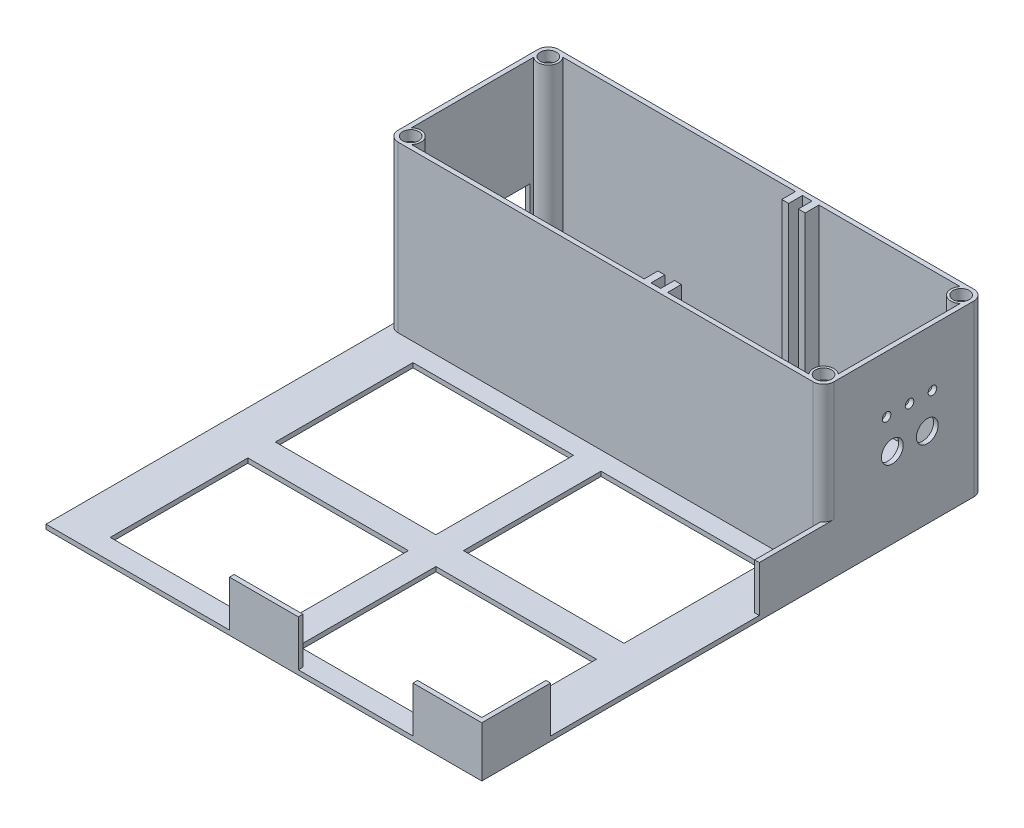
SolidWorks part; units mm, degrees
ref_plane "Front Plane" through (0, 0, 0) normal (0, 0, 1) x (1, 0, 0)
ref_plane "Top Plane" through (0, 0, 0) normal (0, 1, 0) x (1, 0, 0)
ref_plane "Right Plane" through (0, 0, 0) normal (1, 0, 0) x (0, 0, -1)
sketch "Sketch1" plane through (0, 0, 0) normal (0, 1, 0) x (1, 0, 0)
  line L1 (0, 0) -> (190, 0)
  line L2 (0, 0) -> (0, 219)
  line L3 (0, 219) -> (190, 219)
  line L4 (190, 0) -> (190, 219)
  dimension "D1" = 219
  dimension "D2" = 190
extrude "Boss-Extrude1" add sketch "Sketch1" along normal blind 2
sketch "Sketch4" plane through (0, 0, 0) normal (0, 1, 0) x (1, 0, 0)
  line L0 (95, 219) -> (95, 0) construction
  line L3 (190, 219) -> (0, 219) construction
  line L6 (0, 0) -> (190, 0) construction
  line L7 (89, 81) -> (19, 81)
  line L8 (89, 81) -> (89, 141)
  line L9 (89, 141) -> (19, 141)
  line L10 (19, 81) -> (19, 141)
  line L11 (101, 81) -> (171, 81)
  line L12 (101, 81) -> (101, 141)
  line L13 (101, 141) -> (171, 141)
  line L14 (171, 81) -> (171, 141)
  line L15 (101, 69) -> (171, 69)
  line L16 (101, 69) -> (101, 9)
  line L17 (101, 9) -> (171, 9)
  line L18 (171, 69) -> (171, 9)
  line L19 (89, 69) -> (19, 69)
  line L20 (89, 69) -> (89, 9)
  line L21 (89, 9) -> (19, 9)
  line L22 (19, 69) -> (19, 9)
  line L23 (0, 75) -> (190, 75) construction
  line L24 (0, 219) -> (0, 0) construction
  line L25 (190, 0) -> (190, 219) construction
  dimension "D1" = 60
  dimension "D2" = 70
  dimension "D3" = 70
  dimension "D4" = 60
  dimension "D5" = 60
  dimension "D6" = 60
  dimension "D7" = 70
  dimension "D8" = 70
  dimension "D9" = 75
  dimension "D10" = 6
  dimension "D11" = 6
  dimension "D12" = 6
  dimension "D13" = 6
  dimension "D14" = 6
  dimension "D15" = 6
  dimension "D16" = 6
  dimension "D17" = 6
extrude "Cut-Extrude1" cut sketch "Sketch4" along normal blind 4
sketch "Sketch2" plane through (0, 2, 0) normal (0, 1, 0) x (1, 0, 0)
  line L15 (0, 0) -> (190, 0) construction
  line L16 (80, 0) -> (110, 0)
  line L17 (80, 0) -> (80, 2)
  line L18 (80, 2) -> (110, 2)
  line L19 (110, 0) -> (110, 2)
  line L20 (160, 0) -> (190, 0)
  line L21 (190, 0) -> (190, 30)
  line L22 (190, 0) -> (190, 219) construction
  line L23 (190, 30) -> (188, 30)
  line L24 (188, 30) -> (188, 2)
  line L25 (188, 2) -> (160, 2)
  line L26 (160, 2) -> (160, 0)
  line L27 (190, 121) -> (190, 151)
  line L28 (190, 151) -> (156, 151)
  line L29 (156, 151) -> (156, 149)
  line L30 (156, 149) -> (188, 149)
  line L31 (188, 149) -> (188, 121)
  line L32 (188, 121) -> (190, 121)
  dimension "D1" = 2
  dimension "D2" = 30
  dimension "D3" = 80
  dimension "D4" = 2
  dimension "D5" = 2
  dimension "D6" = 30
  dimension "D7" = 30
  dimension "D8" = 2
  dimension "D9" = 2
  dimension "D10" = 30
  dimension "D11" = 34
  dimension "D12" = 147
extrude "Boss-Extrude2" add sketch "Sketch2" along normal blind 20
sketch "Sketch3" plane through (0, 2, 0) normal (0, 1, 0) x (1, 0, 0)
  line L2 (0, 149) -> (190, 149)
  line L4 (188, 217) -> (120, 217)
  line L5 (120, 217) -> (120, 211)
  line L6 (120, 211) -> (117, 211)
  line L7 (117, 211) -> (117, 217)
  line L8 (117, 217) -> (112.8, 217)
  line L9 (112.8, 217) -> (112.8, 211)
  line L10 (112.8, 211) -> (109.8, 211)
  line L11 (109.8, 211) -> (109.8, 217)
  line L12 (109.8, 217) -> (2, 217)
  line L13 (2, 217) -> (2, 151)
  line L14 (2, 151) -> (109.8, 151)
  line L15 (109.8, 151) -> (109.8, 157)
  line L16 (109.8, 157) -> (112.8, 157)
  line L17 (112.8, 157) -> (112.8, 151)
  line L18 (112.8, 151) -> (117, 151)
  line L19 (117, 151) -> (117, 157)
  line L20 (117, 157) -> (120, 157)
  line L21 (120, 157) -> (120, 151)
  line L24 (0, 219) -> (0, 0) construction
  line L25 (0, 149) -> (0, 219)
  line L26 (0, 219) -> (190, 219)
  line L27 (190, 121) -> (190, 151) construction
  line L28 (190, 149) -> (190, 219)
  line L29 (188, 217) -> (188, 151)
  line L30 (190, 151) -> (156, 151) construction
  line L31 (188, 151) -> (120, 151)
  dimension "D1" = 2
  dimension "D2" = 2
  dimension "D3" = 3
  dimension "D4" = 3
  dimension "D5" = 4.2
  dimension "D6" = 3
  dimension "D7" = 3
  dimension "D8" = 4.2
  dimension "D9" = 73
  dimension "D10" = 73
  dimension "D11" = 6
  dimension "D12" = 6
  dimension "D13" = 2
  dimension "D14" = 2
  dimension "D15" = 6
  dimension "D16" = 6
  dimension "D17" = 2
  dimension "D18" = 70
  dimension "D19" = 2
  dimension "D20" = 2
extrude "Boss-Extrude3" add sketch "Sketch3" along normal blind 72
sketch "Sketch7" plane through (0, 2, 0) normal (0, 1, 0) x (1, 0, 0)
  line L0 (2, 151) -> (2, 217) construction
  line L1 (0, 149) -> (188, 149) construction
  line L2 (2, 217) -> (109.8, 217) construction
  circle A0 centre (24, 208) radius 3
  circle A1 centre (24, 160) radius 3
  circle A2 centre (76, 193.5) radius 4.5
  circle A3 centre (76, 165.5) radius 4.5
  dimension "D1" = 6
  dimension "D2" = 6
  dimension "D3" = 9
  dimension "D4" = 9
  dimension "D5" = 52
  dimension "D6" = 48
  dimension "D7" = 28
  dimension "D8" = 22
  dimension "D9" = 9
  dimension "D10" = 16.5
extrude "Boss-Extrude4" add sketch "Sketch7" along normal blind 4
sketch "Sketch8" plane through (0, 6, 0) normal (0, 1, 0) x (1, 0, 0)
  circle A2 centre (76, 193.5) radius 3.5
  circle A3 centre (76, 165.5) radius 3.5
  dimension "D3" = 7
  dimension "D4" = 7
extrude "Cut-Extrude3" cut sketch "Sketch8" against normal blind 4
sketch "Sketch9" plane through (188, 0, 0) normal (-1, 0, 0) x (0, 0, 1)
  circle A0 centre (-204.5, 55.5) radius 2
  circle A1 centre (-163.5, 55.5) radius 2
  circle A2 centre (-204.5, 27) radius 2
  circle A3 centre (-163.5, 27) radius 2
  dimension "D1" = 4
  dimension "D2" = 4
  dimension "D3" = 4
  dimension "D4" = 4
  dimension "D5" = 28.5
  dimension "D6" = 41
  dimension "D7" = 12.5
  dimension "D8" = 25
extrude "Boss-Extrude5" add sketch "Sketch9" along normal blind 2
sketch "Sketch10" plane through (186, 0, 0) normal (-1, 0, 0) x (0, 0, 1)
  circle A0 centre (-204.5, 55.5) radius 0.95
  circle A1 centre (-163.5, 55.5) radius 0.95
  circle A2 centre (-163.5, 27) radius 0.95
  circle A3 centre (-204.5, 27) radius 0.95
  dimension "D1" = 1.9
  dimension "D2" = 1.9
  dimension "D3" = 1.9
  dimension "D4" = 1.9
extrude "Cut-Extrude4" cut sketch "Sketch10" against normal blind 2
sketch "Sketch11" plane through (188, 0, 0) normal (-1, 0, 0) x (0, 0, 1)
  circle A0 centre (-196.5, 49.25) radius 1.875
  circle A1 centre (-186.5, 49.25) radius 1.875
  circle A2 centre (-176.5, 49.25) radius 1.875
  circle A3 centre (-194.25, 35) radius 4.75
  circle A4 centre (-179, 35) radius 4.75
  circle A5 centre (-204.5, 27) radius 0.95 construction
  circle A6 centre (-204.5, 55.5) radius 0.95 construction
  dimension "D1" = 9.5
  dimension "D2" = 9.5
  dimension "D3" = 3.75
  dimension "D4" = 3.75
  dimension "D5" = 3.75
  dimension "D7" = 10.25
  dimension "D8" = 8
  dimension "D10" = 8
  dimension "D6" = 15.25
  dimension "D9" = 6.25
  dimension "D11" = 10
  dimension "D12" = 10
extrude "Cut-Extrude5" cut sketch "Sketch11" against normal blind 4
sketch "Sketch12" plane through (0, 2, 0) normal (0, 1, 0) x (1, 0, 0)
  line L0 (0, 219) -> (0, 149) construction
  line L1 (190, 219) -> (0, 219) construction
  circle A0 centre (5, 214) radius 4.5
  circle A1 centre (5, 154) radius 4.5
  circle A2 centre (185, 214) radius 4.5
  circle A3 centre (185, 154) radius 4.5
  point P8 (0, 0)
  dimension "D1" = 9
  dimension "D4" = 9
  dimension "D5" = 9
  dimension "D8" = 9
  dimension "D2" = 5
  dimension "D3" = 5
  dimension "D6" = 180
  dimension "D7" = 60
extrude "Boss-Extrude6" add sketch "Sketch12" along normal blind 72
sketch "Sketch13" plane through (0, 74, 0) normal (0, 1, 0) x (1, 0, 0)
  circle A0 centre (5, 214) radius 3.5
  circle A1 centre (5, 154) radius 3.5
  circle A2 centre (185, 214) radius 3.5
  circle A3 centre (185, 154) radius 3.5
  dimension "D1" = 7
  dimension "D2" = 7
  dimension "D3" = 7
  dimension "D4" = 7
extrude "Cut-Extrude6" cut sketch "Sketch13" against normal blind 4.5
fillet "Fillet1" radius 4.5 4 edges at (0, 38, -149) (0, 37, -219) (190, 48, -149) (190, 37, -219)
sketch "Sketch14" plane through (0, 0, 0) normal (-1, 0, 0) x (0, 0, 1)
  line L0 (-214.5, 0) -> (0, 0) construction
  line L1 (-209, 12) -> (-191, 12)
  line L2 (-209, 12) -> (-209, 27)
  line L3 (-209, 27) -> (-191, 27)
  line L4 (-191, 12) -> (-191, 27)
  line L11 (-219, 0) -> (-219, 74) construction
  point P6 (0, 0)
  point P7 (0, 0)
  point P8 (0, 0)
  dimension "D1" = 18
  dimension "D2" = 15
  dimension "D3" = 27
  dimension "D4" = 28
extrude "Cut-Extrude7" cut sketch "Sketch14" against normal blind 5
sketch "Sketch15" plane through (0, 6, 0) normal (0, 1, 0) x (1, 0, 0)
  circle A0 centre (24, 208) radius 2.1
  circle A1 centre (24, 160) radius 2.1
  dimension "D1" = 4.2
  dimension "D2" = 4.2
extrude "Boss-Extrude7" add sketch "Sketch15" along normal blind 5.5
